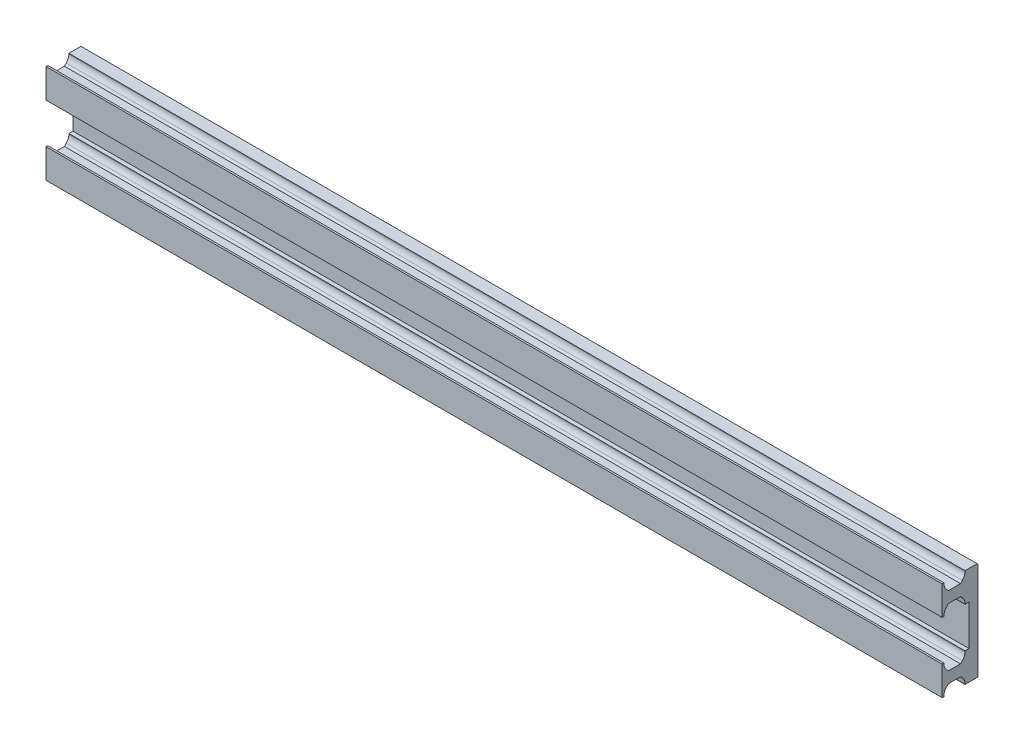
SolidWorks part; units mm, degrees
ref_plane "Front" through (0, 0, 0) normal (0, 0, 1) x (1, 0, 0)
ref_plane "Top" through (0, 0, 0) normal (0, 1, 0) x (1, 0, 0)
ref_plane "Right" through (0, 0, 0) normal (1, 0, 0) x (0, 0, -1)
sketch "Sketch1" plane through (0, 0, 0) normal (0, 0, 1) x (1, 0, 0)
  line L0 (-100, -4) -> (-100, 4) construction
  line L1 (100, 11) -> (-100, 11)
  line L2 (100, 11) -> (100, -11)
  line L3 (100, -11) -> (-100, -11)
  line L4 (-100, 11) -> (-100, -11)
  line L5 (100, 11) -> (-100, -11) construction
  line L6 (100, -11) -> (-100, 11) construction
  line L8 (100, 4) -> (-100, 4) construction
  point P0 (0, 0)
  dimension "D1" = 7
extrude "Boss-Extrude1" add sketch "Sketch1" against normal blind 2
sketch "Sketch2" plane through (0, 0, 0) normal (0, 0, 1) x (1, 0, 0)
  line L0 (-100, 11) -> (-100, -11) construction
  line L1 (100, 11) -> (-100, 11)
  line L2 (100, 11) -> (100, 4.5)
  line L3 (100, 4.5) -> (-100, 4.5)
  line L4 (-100, 11) -> (-100, 4.5)
  line L5 (100, -11) -> (100, 11) construction
  line L6 (100, -11) -> (-100, -11)
  line L7 (100, -11) -> (100, -4.5)
  line L8 (100, -4.5) -> (-100, -4.5)
  line L9 (-100, -11) -> (-100, -4.5)
  line L11 (100, 4) -> (-100, 4) construction
  dimension "D1" = 0.5
extrude "Boss-Extrude2" add sketch "Sketch2" along normal offset from surface (6 mm away) 1
ref_plane "Center of Slots" through (0, 7.75, 0) normal (0, -1, 0) x (-1, 0, 0)
sketch "Sketch5" plane through (0, 0, 0) normal (1, 0, 0) x (0, 0, -1)
  line L16 (-1.9, 6.5) -> (-4.6, 6.5)
  line L17 (-1.9, 6.5) -> (-4.6, 6.5)
  line L18 (-1.4858, 6.0858) -> (-1.9, 6.5)
  line L19 (-1.4858, 6.0858) -> (-1.9, 6.5)
  line L20 (-0.9, 3.8284) -> (-0.9, 4.6716)
  line L21 (-0.9, 3.8284) -> (-0.9, 4.6716)
  line L22 (-1.9, 2) -> (-1.4858, 2.4142)
  line L23 (-1.9, 2) -> (-1.4858, 2.4142)
  line L24 (-4.6, 2) -> (-1.9, 2)
  line L25 (-4.6, 2) -> (-1.9, 2)
  line L26 (-5.0142, 2.4142) -> (-4.6, 2)
  line L27 (-5.0142, 2.4142) -> (-4.6, 2)
  line L28 (-5.6, 4.6716) -> (-5.6, 3.8284)
  line L29 (-5.6, 4.6716) -> (-5.6, 3.8284)
  line L30 (-4.6, 6.5) -> (-5.0142, 6.0858)
  line L31 (-4.6, 6.5) -> (-5.0142, 6.0858)
  arc A12 (-0.9, 4.6716) -> (-1.4858, 6.0858) centre (-2.9, 4.6716) ccw
  arc A13 (-0.9, 4.6716) -> (-1.4858, 6.0858) centre (-2.9, 4.6716) ccw
  arc A14 (-1.4858, 2.4142) -> (-0.9, 3.8284) centre (-2.9, 3.8284) ccw
  arc A15 (-1.4858, 2.4142) -> (-0.9, 3.8284) centre (-2.9, 3.8284) ccw
  arc A16 (-5.6, 3.8284) -> (-5.0142, 2.4142) centre (-3.6, 3.8284) ccw
  arc A17 (-5.6, 3.8284) -> (-5.0142, 2.4142) centre (-3.6, 3.8284) ccw
  arc A18 (-5.0142, 6.0858) -> (-5.6, 4.6716) centre (-3.6, 4.6716) ccw
  arc A19 (-5.0142, 6.0858) -> (-5.6, 4.6716) centre (-3.6, 4.6716) ccw
  dimension "D1" = 0
extrude "Slot 1" cut sketch "Sketch5" against normal through all both and the other way through all
mirror "Slot 1x2" about plane through (0, 7.75, 0) normal (0, -1, 0) of "Slot 1"
mirror "Slot 2" about plane through (0, 0, 0) normal (0, 1, 0) of "Slot 1x2", "Slot 1"
chamfer "Deburs" distance 0.2 angle 45 2 edges at (0, -11, -2) (0, 11, -2)
